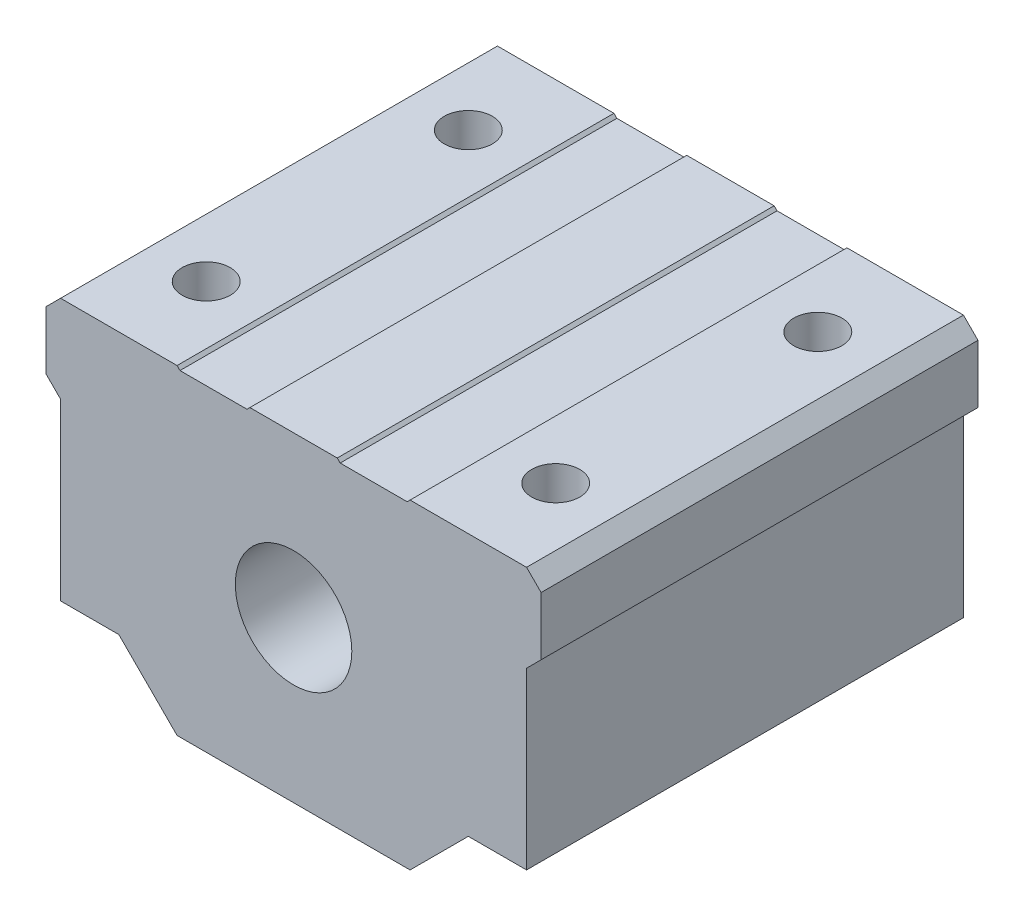
SolidWorks part; units mm, degrees
ref_plane "Front Plane" through (0, 0, 0) normal (0, 0, 1) x (1, 0, 0)
ref_plane "Top Plane" through (0, 0, 0) normal (0, 1, 0) x (1, 0, 0)
ref_plane "Right Plane" through (0, 0, 0) normal (1, 0, 0) x (0, 0, -1)
sketch "Sketch1" plane through (0, 0, 0) normal (0, 0, 1) x (1, 0, 0)
  line L0 (0, 0) -> (0, 25715.025) construction
  line L1 (8, 0) -> (-8, 0)
  line L2 (-8, 0) -> (-12, 4)
  line L3 (-12, 4) -> (-16, 4)
  line L4 (-16, 4) -> (-16, 16)
  line L5 (-16, 16) -> (-17, 16)
  line L6 (-17, 16) -> (-17, 22)
  line L7 (-17, 22) -> (17, 22)
  line L9 (17, 16) -> (17, 22)
  line L10 (16, 16) -> (17, 16)
  line L11 (16, 4) -> (16, 16)
  line L12 (12, 4) -> (16, 4)
  line L13 (8, 0) -> (12, 4)
  point P12 (0, 22)
  point P17 (0, 0)
  dimension "D1" = 22
  dimension "D2" = 18
  dimension "D3" = 6
  dimension "D4" = 34
  dimension "D5" = 1
  dimension "D6" = 16
  dimension "D7" = 45
extrude "Boss-Extrude1" add sketch "Sketch1" along normal blind 30
sketch "Sketch2" plane through (0, 0, 30) normal (0, 0, 1) x (1, 0, 0)
  line L0 (0, 22) -> (0, 0) construction
  line L1 (17, 22) -> (-17, 22) construction
  circle A0 centre (0, 11) radius 4
  dimension "D1" = 11
  dimension "D2" = 8
extrude "Cut-Extrude1" cut sketch "Sketch2" against normal through all
chamfer "Chamfer1" distance 1 angle 45 4 edges at (-17, 16, 15) (17, 16, 15) (-17, 22, 15) (17, 22, 15)
sketch "Sketch3" plane through (0, 22, 0) normal (0, 1, 0) x (1, 0, 0)
  line L0 (0, 0) -> (0, -30) construction
  line L1 (16, -30) -> (-16, -30) construction
  line L3 (-12, -24) -> (12, -24) construction
  line L4 (-12, -24) -> (-12, -6) construction
  line L5 (-12, -6) -> (12, -6) construction
  line L6 (12, -24) -> (12, -6) construction
  line L7 (-12, -24) -> (12, -6) construction
  line L8 (-12, -6) -> (12, -24) construction
  point P5 (0, -15)
  dimension "D1" = 18
  dimension "D2" = 24
sketch "Sketch7" plane through (0, 22, 0) normal (0, 1, 0) x (1, 0, 0)
  circle A0 centre (-12, -6) radius 1.5
  circle A1 centre (-12, -24) radius 1.5
  circle A2 centre (12, -6) radius 1.5
  circle A3 centre (12, -24) radius 1.5
  dimension "D1" = 3
extrude "Cut-Extrude3" cut sketch "Sketch7" against normal through all and the other way through all
hole_wizard "M4 Tapped Hole1" positions "Sketch4" profile "Sketch5" tap size "M4" standard "ISO"
sketch "Sketch4" plane through (0, 22, 0) normal (0, 1, 0) x (1, 0, 0)
  point P0 (-12, -6)
  point P3 (12, -6)
  point P6 (-12, -24)
  point P9 (12, -24)
sketch "Sketch5" plane through (-12, 22, 6) normal (1, 0, 0) x (0, 0, 1)
  line L0 (0, 0) -> (0, 8.9914)
  line L1 (0, 8.9914) -> (1.65, 8)
  line L2 (1.65, 8) -> (1.65, 0)
  line L5 (1.65, 0) -> (0, 0)
  line L10 (0, 8.9914) -> (-1.65, 8) construction
  line L11 (0, -6.35) -> (0, 107.95) construction
  dimension "Tap Drill Dia." = 3.3
  dimension "Tap Drill Depth" = 8
  dimension "Drill Angle" = 118
cosmetic thread "Hole Thread5" parameters "D1"=8, "D2"=4
cosmetic thread "Hole Thread6" parameters "D1"=8, "D2"=4
cosmetic thread "Hole Thread7" parameters "D1"=8, "D2"=4
cosmetic thread "Hole Thread8" parameters "D1"=8, "D2"=4
sketch "Sketch8" plane through (0, 0, 0) normal (0, 0, -1) x (-1, 0, 0)
  line L0 (-8, 22) -> (-7.8, 21.8)
  line L1 (-16, 22) -> (16, 22) construction
  line L2 (-7.8, 21.8) -> (-3.2, 21.8)
  line L3 (-3.2, 21.8) -> (-3, 22)
  line L4 (-3, 22) -> (-8, 22)
  line L5 (-5.5, 22) -> (-5.5, 21.8) construction
  line L6 (0, 22) -> (0, 0) construction
  line L7 (8, 0) -> (-8, 0) construction
  line L8 (-12, 14) -> (-12, 22) construction
  line L9 (-13.65, 14) -> (-10.35, 14) construction
  line L10 (-7.8, 21.8) -> (-8, 22)
  line L11 (-3, 22) -> (-3.2, 21.8)
  line L12 (5.5, 22) -> (5.5, 21.8) construction
  line L13 (3, 22) -> (3.2, 21.8)
  line L14 (7.8, 21.8) -> (8, 22)
  line L15 (3, 22) -> (8, 22)
  line L16 (3.2, 21.8) -> (3, 22)
  line L17 (7.8, 21.8) -> (3.2, 21.8)
  line L18 (8, 22) -> (7.8, 21.8)
  line M12 (16, 22) -> (-16, 22)
  dimension "D1" = 5
  dimension "D2" = 4
  dimension "D3" = 0.2
extrude "Cut-Extrude4" cut sketch "Sketch8" against normal through all contours L17 L14 L13 M12 | L2 L3 L0 M12 region at (5.5, 21.9014, 0) region at (-5.5, 21.9014, 0)
